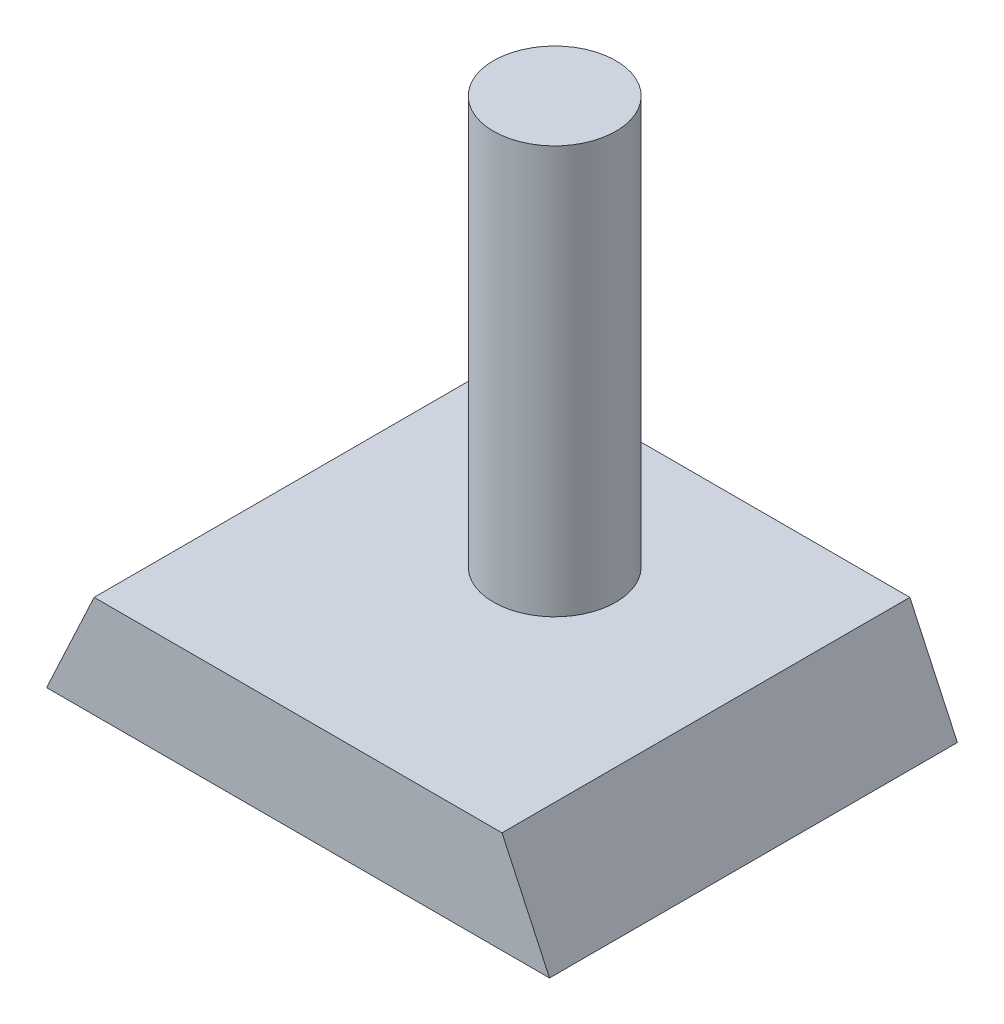
SolidWorks part; units mm, degrees
ref_plane "Front Plane" through (0, 0, 0) normal (0, 0, 1) x (1, 0, 0)
ref_plane "Top Plane" through (0, 0, 0) normal (0, 1, 0) x (1, 0, 0)
ref_plane "Right Plane" through (0, 0, 0) normal (1, 0, 0) x (0, 0, -1)
sketch "Sketch1" plane through (0, 0, 0) normal (0, 0, 1) x (1, 0, 0)
  line L0 (-7.8305, 0) -> (7.8305, 0)
  line L1 (7.8305, 0) -> (6.35, 3.175)
  line L2 (6.35, 3.175) -> (-6.35, 3.175)
  line L3 (-6.35, 3.175) -> (-7.8305, 0)
  point P4 (-9.9714, 0)
  dimension "D1" = 3.175
  dimension "D2" = 12.7
  dimension "D3" = 65
extrude "Boss-Extrude1" add sketch "Sketch1" along normal blind 12.7
sketch "Sketch2" plane through (0, 3.175, 0) normal (0, 1, 0) x (1, 0, 0)
  circle A0 centre (0, -4.7088) radius 1.905
  dimension "D1" = 3.81
extrude "Boss-Extrude2" add sketch "Sketch2" along normal blind 12.7
